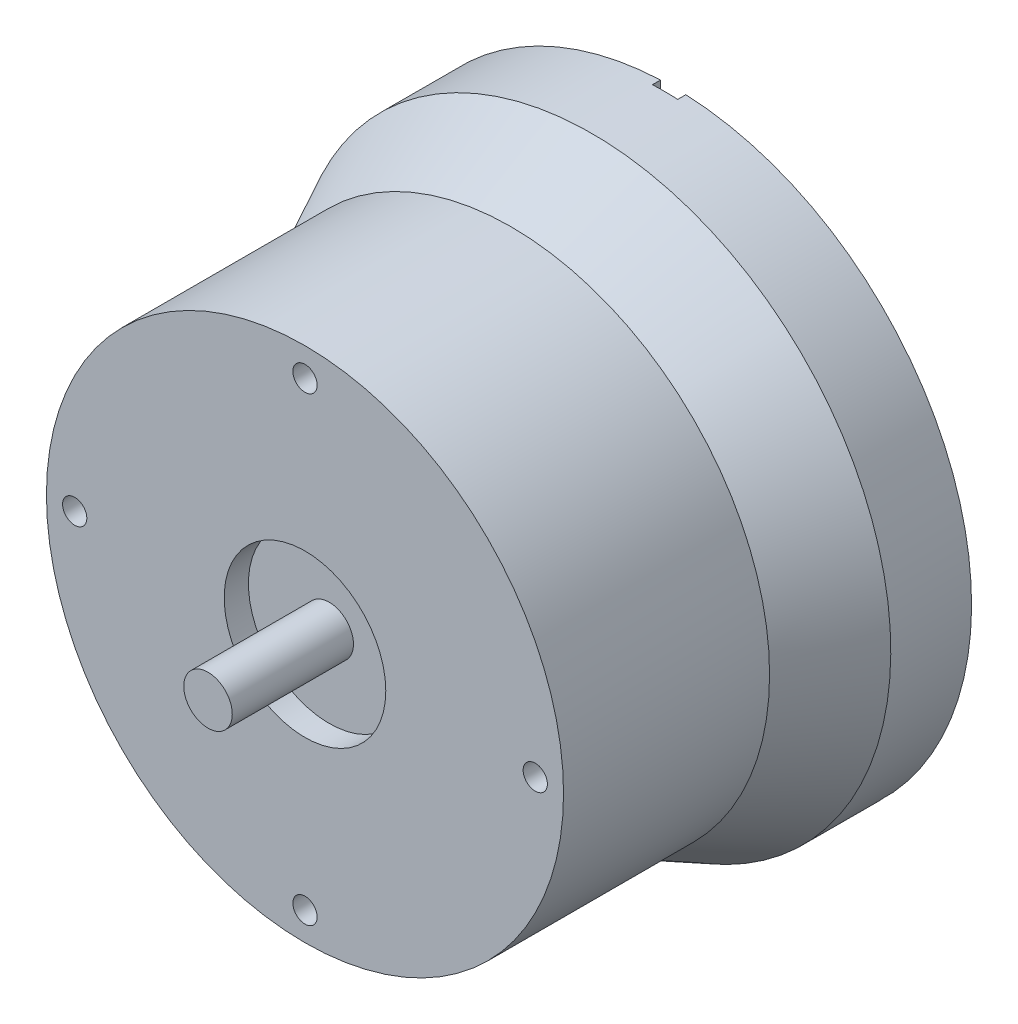
SolidWorks part; units mm, degrees
material "1060-H12 棒材(SS)"
ref_plane "前视基准面" through (0, 0, 0) normal (0, 0, 1) x (1, 0, 0)
ref_plane "上视基准面" through (0, 0, 0) normal (0, 1, 0) x (1, 0, 0)
ref_plane "右视基准面" through (0, 0, 0) normal (1, 0, 0) x (0, 0, -1)
other "Configuration Table"
sketch "草图1" plane through (0, 0, 0) normal (0, 0, 1) x (1, 0, 0)
  circle A0 centre (0, 0) radius 32
extrude "凸台-拉伸1" add sketch "草图1" against normal blind 25.5
ref_plane "基准面1" through (0, 0, -35.5) normal (0, 0, -1) x (-1, 0, 0)
sketch "草图3" plane through (0, 0, -35.5) normal (0, 0, -1) x (-1, 0, 0)
  circle A0 centre (0, 0) radius 37
extrude "凸台-拉伸3" add sketch "草图3" along normal blind 10 separate body
loft "放样1" add section edge at (32, 0, -25.5) section edge at (-37, 0, -35.5) connector at (30.1488, 10.726, -25.5) connector at (33.7219, 15.226, -35.5)
sketch "草图4" plane through (0, 0, 0) normal (0, 0, 1) x (1, 0, 0)
  line L0 (0, 0) -> (28.5, 0)
  line L1 (0, 0) -> (-28.5, 0)
  line L2 (0, 0) -> (0, 28.5)
  line L3 (0, 0) -> (0, -28.5)
  circle A0 centre (0, 0) radius 28.5
  circle A1 centre (28.5, 0) radius 1.5
  circle A2 centre (0, -28.5) radius 1.5
  circle A3 centre (-28.5, 0) radius 1.5
  circle A4 centre (0, 28.5) radius 1.5
extrude "切除-拉伸1" cut sketch "草图4" against normal blind 10 contours A0 A1 | L0 A1 A0 | A0 A1 L0 | L2 A4 A0 | A0 A4 L2 | A0 A4 | A0 A3 L1 | A0 A3 | L1 A3 A0 | A0 A2 | A0 A2 L3 | L3 A2 A0 region at (27.8563, 0.6311, 0) region at (27.8563, -0.6311, 0) region at (-27.8563, -0.6311, 0) region at (-27.8563, 0.6311, 0) region at (-0.6311, 27.8563, 0) region at (0.6311, 27.8563, 0) region at (0.6311, -27.8563, 0) region at (-0.6311, -27.8563, 0) region at (29.1295, 0, 0) region at (-29.1295, 0, 0) region at (0, 29.1295, 0) region at (0, -29.1295, 0)
sketch "草图5" plane through (0, 0, -45.5) normal (0, 0, -1) x (-1, 0, 0)
  line L0 (0, 0) -> (0, 10)
  line L1 (0, 10) -> (-31.4484, 10)
  line L3 (-31.4484, -10) -> (0, -10)
  line L4 (0, -10) -> (0, 0)
  line L5 (0, 10) -> (20, 10)
  line L6 (20, 10) -> (20, -10)
  line L7 (20, -10) -> (0, -10)
  circle A1 centre (0, 0) radius 33
  dimension "D1" = 10
  dimension "D2" = 10
  dimension "D4" = 20
extrude "切除-拉伸2" cut sketch "草图5" against normal blind 5 contours L1 A1 L3 L4 L0 | L7 L6 L5 L0 L4 region at (16.2471, 0, -45.5) region at (-10, 0, -45.5)
sketch "草图7" plane through (0, 0, -45.5) normal (0, 0, -1) x (-1, 0, 0)
  line L0 (20, 10) -> (20, -10) construction
  line L2 (20, 5) -> (28, 5)
  line L3 (20, -5) -> (28, -5)
  circle A0 centre (20, 0) radius 5
  circle A1 centre (28, 5) radius 3
  circle A2 centre (28, -5) radius 3
  dimension "D1" = 8
  dimension "D2" = 8
extrude "凸台-拉伸4" add sketch "草图7" along normal blind 10 contours A1 | A2 region at (-28, 7.9151, -45.5) region at (-28, -2.0849, -45.5)
sketch "草图8" plane through (0, 0, -45.5) normal (0, 0, -1) x (-1, 0, 0)
  line L0 (0, 0) -> (0, 37)
  line L1 (0, 0) -> (0, -37)
  line L2 (0, 0) -> (37, 0)
  line L3 (0, 0) -> (-37, 0)
  line L4 (0, 0) -> (26.163, -26.163)
  line L5 (0, 0) -> (-26.163, -26.163)
  line L6 (26.163, -26.163) -> (24.0416, -24.0416)
  line L7 (-26.163, -26.163) -> (-24.0416, -24.0416)
  line L8 (0, 37) -> (0, 34)
  line L9 (-24.0416, -24.0416) -> (-22.981, -25.1023)
  line L10 (-22.981, -25.1023) -> (-25.081, -27.2019)
  line L11 (-24.0416, -24.0416) -> (-25.1023, -22.981)
  line L12 (-25.1023, -22.981) -> (-27.2907, -24.9844)
  line L13 (24.0416, -24.0416) -> (22.981, -25.1023)
  line L14 (22.981, -25.1023) -> (25.0808, -27.2021)
  line L15 (24.0416, -24.0416) -> (25.1023, -22.981)
  line L16 (25.1023, -22.981) -> (27.2021, -25.0808)
  line L17 (0, 34) -> (1.5, 34)
  line L18 (1.5, 34) -> (1.5, 36.9696)
  line L19 (0, 34) -> (-1.499, 33.9453)
  line L20 (-1.499, 33.9453) -> (-1.6323, 36.964)
  circle A0 centre (0, 0) radius 37 construction
  circle A1 centre (24.0416, -24.0416) radius 1.5
  circle A2 centre (-24.0416, -24.0416) radius 1.5
  circle A3 centre (0, 34) radius 1.5
  circle A4 centre (0, 0) radius 37
  circle M7 centre (0, 0) radius 37
extrude "切除-拉伸3" cut sketch "草图8" against normal blind 1 contours A3 L8 L20 M7 | A3 L18 L8 M7 | A1 L6 L16 M7 | A1 L14 L6 M7 | A2 L7 L10 M7 | A2 L12 L7 M7 region at (0.8708, 36.0472, -45.5) region at (-0.8216, 36.0531, -45.5) region at (24.9125, -26.0743, -45.5) region at (-24.9124, -26.0743, -45.5) region at (-26.0743, -24.9124, -45.5) region at (26.1048, -24.8748, -45.5)
extrude "切除-拉伸4" cut sketch "草图8<3>" against normal blind 3 contours L5 A2 L9 | L9 A2 L5 | L11 A2 L5 | L5 A2 L11 | L4 A1 L15 | L13 A1 L4 | L15 A1 L4 | L4 A1 L13 | L0 A3 L17 | L19 A3 L0 | L0 A3 L19 | L17 A3 L0 region at (0.628, 33.3487, -45.5) region at (-0.6366, 33.3634, -45.5) region at (-24.0416, -23.1413, -45.5) region at (-23.1413, -24.0416, -45.5) region at (23.1413, -24.0416, -45.5) region at (24.0416, -23.1413, -45.5) region at (0.6449, 34.6218, -45.5) region at (-0.6366, 34.6366, -45.5) region at (-24.9419, -24.0416, -45.5) region at (-24.0416, -24.9419, -45.5) region at (24.0416, -24.9419, -45.5) region at (24.9419, -24.0416, -45.5)
sketch "草图8<3>" plane through (0, 0, -45.5) normal (0, 0, -1) x (-1, 0, 0) same geometry as "草图8"
sketch "草图9" plane through (0, 0, 0) normal (0, 0, 1) x (1, 0, 0)
  circle A0 centre (0, 0) radius 10
  circle A1 centre (0, 0) radius 3
extrude "切除-拉伸5" cut sketch "草图9" against normal blind 3
extrude "凸台-拉伸5" add sketch "草图9<4>" along normal blind 12 contours A1 region at (0, 0, 0)
sketch "草图9<4>" plane through (0, 0, 0) normal (0, 0, 1) x (1, 0, 0) same geometry as "草图9"
